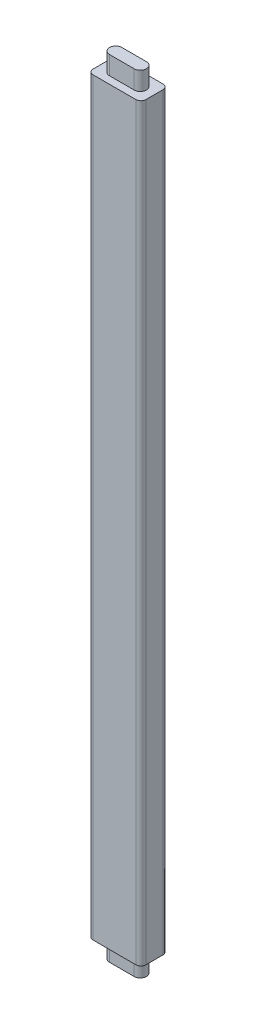
SolidWorks part; units mm, degrees
ref_plane "Front" through (0, 0, 0) normal (0, 0, 1) x (1, 0, 0)
ref_plane "Top" through (0, 0, 0) normal (0, 1, 0) x (1, 0, 0)
ref_plane "Right" through (0, 0, 0) normal (1, 0, 0) x (0, 0, -1)
sketch "Esquisse1" plane through (0, 0, 0) normal (0, 1, 0) x (1, 0, 0)
  line L1 (0, 0) -> (43, 0)
  line L2 (0, 0) -> (0, 22)
  line L3 (0, 22) -> (43, 22)
  line L4 (43, 0) -> (43, 22)
  dimension "D1" = 43
  dimension "D2" = 22
extrude "Boss.-Extru.1" add sketch "Esquisse1" along normal blind 610
sketch "Esquisse2" plane through (0, 610, 0) normal (0, 1, 0) x (1, 0, 0)
  line L0 (43, 11) -> (0, 11) construction
  line L1 (43, 0) -> (43, 22) construction
  line L2 (0, 22) -> (0, 0) construction
  line L3 (11.5, 11) -> (31.5, 11) construction
  line L4 (11.5, 16) -> (31.5, 16)
  line L5 (11.5, 6) -> (31.5, 6)
  arc A0 (11.5, 16) -> (11.5, 6) centre (11.5, 11) ccw
  arc A1 (31.5, 6) -> (31.5, 16) centre (31.5, 11) ccw
  point P8 (21.5, 11)
  dimension "D1" = 10
  dimension "D2" = 20
extrude "Boss.-Extru.2" add sketch "Esquisse2" along normal blind 15
extrude "Boss.-Extru.3" add sketch "Esquisse2<2>" against normal blind 15 from vertex starting at point (43, 0, 0)
sketch "Esquisse2<2>" plane through (0, 610, 0) normal (0, 1, 0) x (1, 0, 0) same geometry as "Esquisse2"
fillet "Congé1" radius 4 4 edges at (43, 305, 0) (43, 305, -22) (0, 305, -22) (0, 305, 0)
